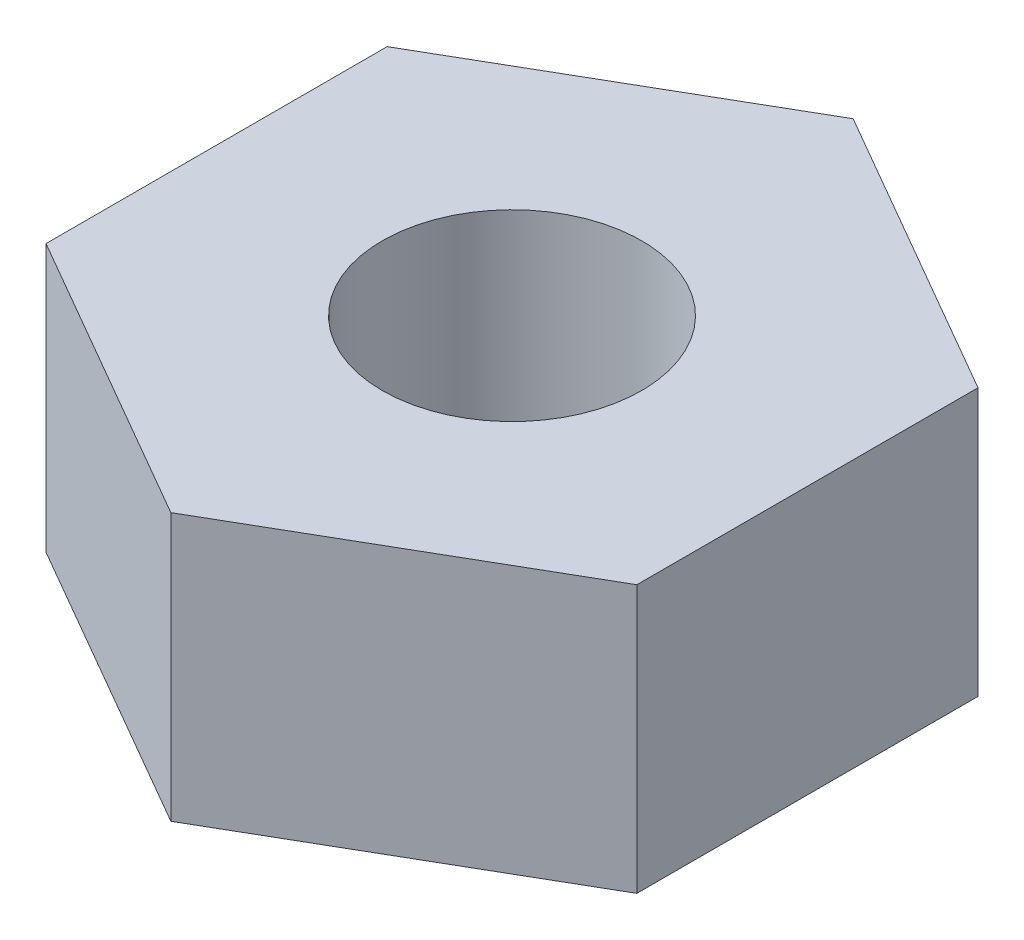
SolidWorks part; units mm, degrees
ref_plane "Front Plane" through (0, 0, 0) normal (0, 0, 1) x (1, 0, 0)
ref_plane "Top Plane" through (0, 0, 0) normal (0, 1, 0) x (1, 0, 0)
ref_plane "Right Plane" through (0, 0, 0) normal (1, 0, 0) x (0, 0, -1)
sketch "Sketch1" plane through (0, 0, 0) normal (0, 1, 0) x (1, 0, 0)
  line L1 (0, -3.9433) -> (3.415, -1.9717)
  line L2 (3.415, -1.9717) -> (3.415, 1.9717)
  line L3 (3.415, 1.9717) -> (0, 3.9433)
  line L4 (0, 3.9433) -> (-3.415, 1.9717)
  line L5 (-3.415, 1.9717) -> (-3.415, -1.9717)
  line L6 (-3.415, -1.9717) -> (0, -3.9433)
  circle A0 centre (0, 0) radius 3.415 construction
  circle A1 centre (0, 0) radius 1.5
  dimension "D2" = 3
  dimension "D1" = 6.83
extrude "Boss-Extrude1" add sketch "Sketch1" along normal blind 3.09
